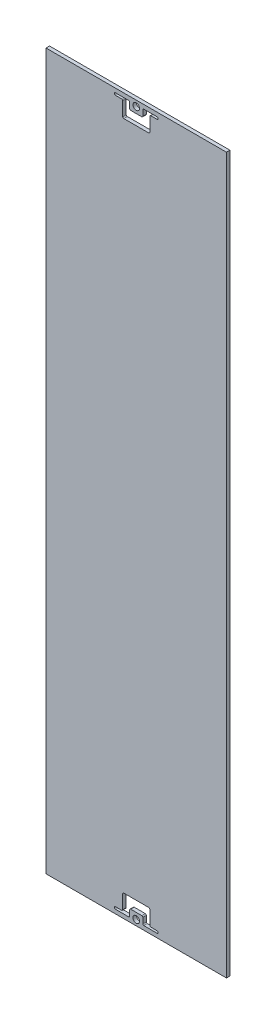
SolidWorks part; units mm, degrees
material "FR4_stuffedProtoboard"
ref_plane "Front Plane" through (0, 0, 0) normal (0, 0, 1) x (1, 0, 0)
ref_plane "Top Plane" through (0, 0, 0) normal (0, 1, 0) x (1, 0, 0)
ref_plane "Right Plane" through (0, 0, 0) normal (1, 0, 0) x (0, 0, -1)
sketch "Sketch1" plane through (0, 0, 0) normal (0, 0, 1) x (1, 0, 0)
  line L1 (-41.25, 163.5) -> (41.25, 163.5)
  line L2 (-41.25, 163.5) -> (-41.25, -163.5)
  line L3 (-41.25, -163.5) -> (41.25, -163.5)
  line L4 (41.25, 163.5) -> (41.25, -163.5)
  line L5 (-41.25, 163.5) -> (41.25, -163.5) construction
  line L6 (-41.25, -163.5) -> (41.25, 163.5) construction
  point P0 (0, 0)
  point P5 (0, 0)
  dimension "D1" = 82.5
  dimension "D2" = 327
extrude "PCB Extrude" add sketch "Sketch1" along normal blind 1.6
sketch "Solar Hole sketch" plane through (0, 0, 0) normal (0, 0, 1) x (1, 0, 0)
  line L0 (-5.7, -153.35) -> (5.7, -153.35)
  line L1 (-6.2, -160.15) -> (-6.2, -153.85)
  line L2 (-9.5, -160.65) -> (-6.7, -160.65)
  line L3 (-3.5, -161.65) -> (-9.5, -161.65)
  line L4 (-3, -158.65) -> (-3, -161.15)
  line L5 (2.5, -158.15) -> (-2.5, -158.15)
  line L6 (3, -161.15) -> (3, -158.65)
  line L7 (9.5, -161.65) -> (3.5, -161.65)
  line L8 (6.7, -160.65) -> (9.5, -160.65)
  line L9 (6.2, -153.85) -> (6.2, -160.15)
  arc A0 (6.2, -153.85) -> (5.7, -153.35) centre (5.7, -153.85) ccw
  arc A1 (-5.7, -153.35) -> (-6.2, -153.85) centre (-5.7, -153.85) ccw
  arc A2 (-6.7, -160.65) -> (-6.2, -160.15) centre (-6.7, -160.15) ccw
  arc A3 (-9.5, -160.65) -> (-9.5, -161.65) centre (-9.5, -161.15) ccw
  arc A4 (-3.5, -161.65) -> (-3, -161.15) centre (-3.5, -161.15) ccw
  arc A5 (-2.5, -158.15) -> (-3, -158.65) centre (-2.5, -158.65) ccw
  arc A6 (3, -158.65) -> (2.5, -158.15) centre (2.5, -158.65) ccw
  arc A7 (3, -161.15) -> (3.5, -161.65) centre (3.5, -161.15) ccw
  arc A8 (9.5, -161.65) -> (9.5, -160.65) centre (9.5, -161.15) ccw
  arc A9 (6.2, -160.15) -> (6.7, -160.65) centre (6.7, -160.15) ccw
  circle A10 centre (0, -160.95) radius 1.5
  point P0 (0, 0)
  point P37 (0, 0)
  point P38 (0, 0)
  point P39 (-6.0536, -153.4964)
  point P40 (0, 0)
  point P42 (-9.4615, -154.4398)
extrude "Solar Hole" cut sketch "Solar Hole sketch" along normal through all
mirror "Mirror Solar Hole" about plane through (0, 0, 0) normal (0, 1, 0) of "Solar Hole"
